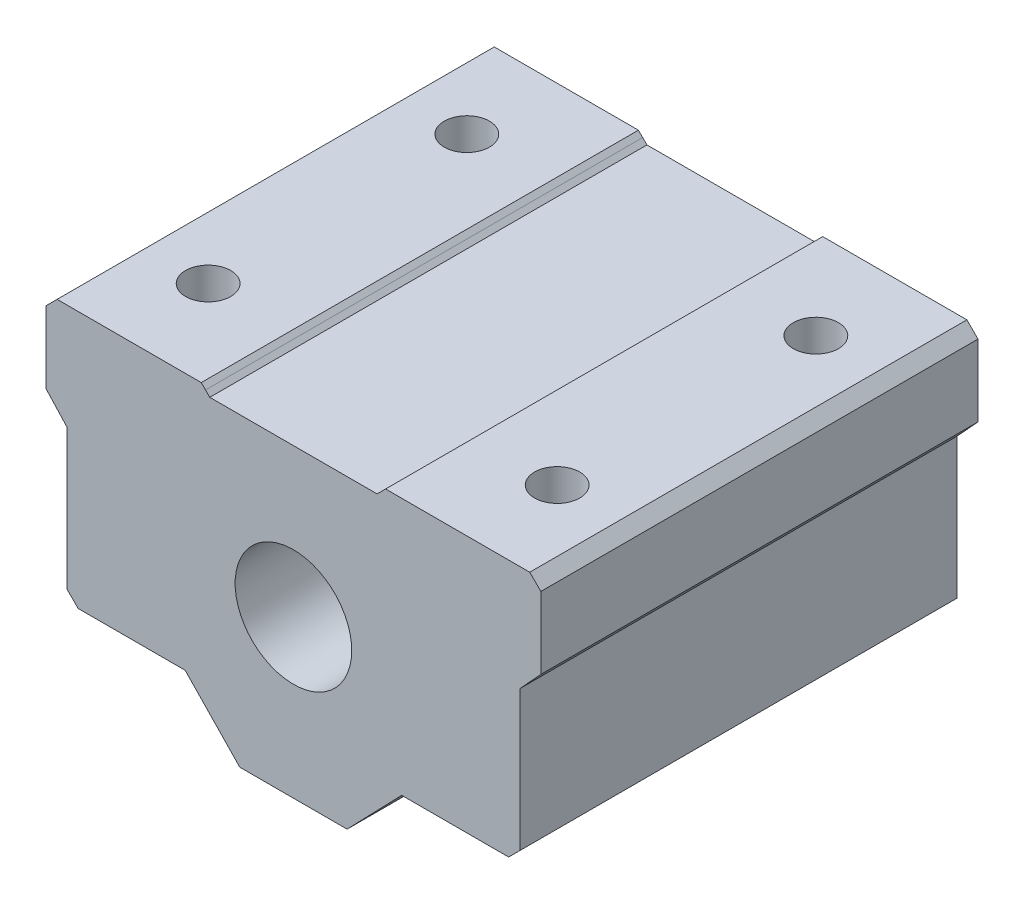
SolidWorks part; units mm, degrees
ref_plane "Front Plane" through (0, 0, 0) normal (0, 0, 1) x (1, 0, 0)
ref_plane "Top Plane" through (0, 0, 0) normal (0, 1, 0) x (1, 0, 0)
ref_plane "Right Plane" through (0, 0, 0) normal (1, 0, 0) x (0, 0, -1)
sketch "Sketch1" plane through (0, 0, 0) normal (0, 0, 1) x (1, 0, 0)
  line L0 (0, 0) -> (33.9598, 0)
  line L1 (33.9598, 0) -> (33.9598, -17.653)
  line L2 (33.9598, -17.653) -> (24.4094, -17.653)
  line L3 (24.4094, -17.653) -> (20.6629, -21.5392)
  line L4 (20.6629, -21.5392) -> (13.2969, -21.5392)
  line L5 (13.2969, -21.5392) -> (9.5504, -17.653)
  line L6 (9.5504, -17.653) -> (0, -17.653)
  line L7 (0, -17.653) -> (0, 0)
  line L8 (16.9799, -10.7696) -> (16.9799, 0) construction
  line L9 (16.9799, -10.7696) -> (16.9799, -21.5392) construction
  circle A0 centre (16.9799, -10.7696) radius 4
  dimension "D1" = 8
  dimension "D2" = 33.9598
  dimension "D3" = 17.653
  dimension "D4" = 21.5392
  dimension "D5" = 7.366
  dimension "D6" = 14.859
extrude "Boss-Extrude1" add sketch "Sketch1" along normal blind 30
sketch "Sketch2" plane through (0, -17.653, 0) normal (0, -1, 0) x (-1, 0, 0)
  line L0 (-5.0038, -23.8773) -> (0, -23.8773) construction
  line L1 (0, -30) -> (0, 0) construction
  line L2 (-28.956, -23.8773) -> (-33.9598, -23.8773) construction
  line L3 (-33.9598, -30) -> (-33.9598, 0) construction
  line L4 (-28.956, -6.1227) -> (-33.9598, -6.1227) construction
  line L5 (-5.0038, -6.1227) -> (0, -6.1227) construction
  line L6 (-5.0038, -23.8773) -> (-5.0038, -30) construction
  line L7 (0, -30) -> (-9.5504, -30) construction
  line L8 (-28.956, -23.8773) -> (-28.956, -30) construction
  line L9 (-24.4094, -30) -> (-33.9598, -30) construction
  line L10 (-28.956, -6.1227) -> (-28.956, 0) construction
  line L11 (-24.4094, 0) -> (-33.9598, 0) construction
  line L12 (-5.0038, -6.1227) -> (-5.0038, 0) construction
  line L13 (0, 0) -> (-9.5504, 0) construction
  line L14 (-5.0038, -22.3279) -> (-5.0038, -7.6721) construction
  line L15 (-6.5532, -23.8773) -> (-27.4066, -23.8773) construction
  circle A0 centre (-5.0038, -23.8773) radius 1.5494
  circle A1 centre (-5.0038, -6.1227) radius 1.5494
  circle A2 centre (-28.956, -6.1227) radius 1.5494
  circle A3 centre (-28.956, -23.8773) radius 1.5494
  dimension "D3" = 3.0988
  dimension "D1" = 20.8534
  dimension "D2" = 14.6558
extrude "Cut-Extrude1" cut sketch "Sketch2" against normal through all
sketch "Sketch3" plane through (0, 0, 0) normal (0, 1, 0) x (1, 0, 0)
  line L0 (33.9598, -30) -> (0, -30) construction
  line L1 (10.9474, -30) -> (23.0124, -30)
  line L2 (10.9474, -30) -> (10.9474, 0)
  line L3 (10.9474, 0) -> (23.0124, 0)
  line L4 (23.0124, -30) -> (23.0124, 0)
  line L5 (33.9598, 0) -> (0, 0) construction
  line L6 (33.9598, -15) -> (23.0124, -15) construction
  line L7 (33.9598, -30) -> (33.9598, 0) construction
  line L8 (10.9474, -15) -> (0, -15) construction
  line L9 (0, -30) -> (0, 0) construction
  dimension "D1" = 12.065
extrude "Cut-Extrude2" cut sketch "Sketch3" against normal blind 0.5842
chamfer "Chamfer1" distance 0.2921 angle 45 4 edges at (23.0124, -0.5842, 15) (23.0124, 0, 15) (10.9474, -0.5842, 15) (10.9474, 0, 15)
sketch "Sketch4" plane through (0, 0, 30) normal (0, 0, 1) x (1, 0, 0)
  line L0 (1.4478, -17.653) -> (1.4478, -7.2644)
  line L1 (0, -17.653) -> (9.5504, -17.653) construction
  line L2 (1.4478, -7.2644) -> (0, -5.6896)
  line L3 (0, 0) -> (0, -17.653) construction
  line L4 (0, -5.6896) -> (0, -17.653)
  line L5 (0, -17.653) -> (1.4478, -17.653)
  line L6 (10.6553, 0) -> (0, 0) construction
  dimension "D1" = 1.4478
  dimension "D2" = 10.3886
  dimension "D3" = 5.6896
extrude "Cut-Extrude3" cut sketch "Sketch4" against normal through all
ref_plane "Plane1" through (16.9799, 0, 0) normal (-1, 0, 0) x (0, 0, 1)
mirror "Mirror1" about plane through (16.9799, 0, 0) normal (-1, 0, 0) of "Cut-Extrude3"
chamfer "Chamfer2" distance 0.762 angle 45 4 edges at (32.512, -17.653, 15) (1.4478, -17.653, 15) (33.9598, 0, 15) (0, 0, 15)
